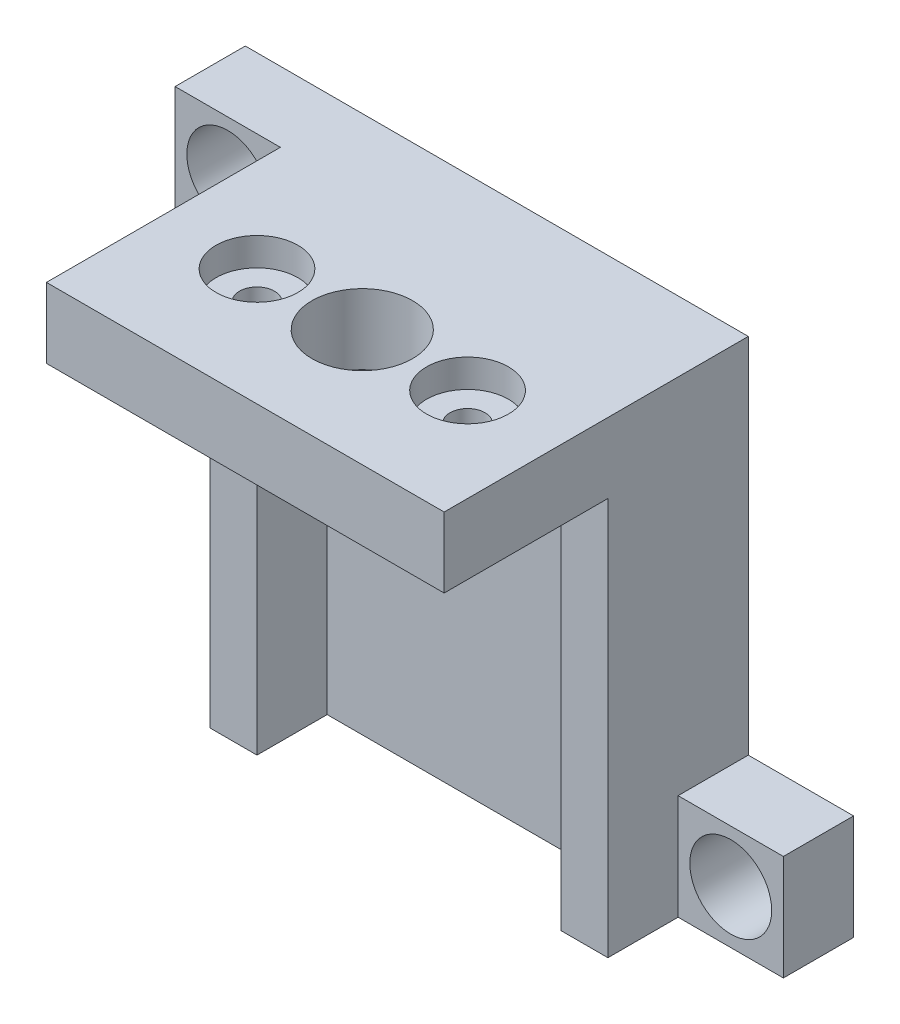
SolidWorks part; units mm, degrees
ref_plane "Front Plane" through (0, 0, 0) normal (0, 0, 1) x (1, 0, 0)
ref_plane "Top Plane" through (0, 0, 0) normal (0, 1, 0) x (1, 0, 0)
ref_plane "Right Plane" through (0, 0, 0) normal (1, 0, 0) x (0, 0, -1)
sketch "Sketch1" plane through (0, 0, 0) normal (0, 0, 1) x (1, 0, 0)
  line L5 (0, 0) -> (17, 0)
  line L6 (0, 0) -> (0, 15.5)
  line L11 (0, 20) -> (17, 20)
  line L12 (17, 4.5) -> (17, 20)
  line L17 (0, 0) -> (17, 20) construction
  line L18 (0, 20) -> (17, 0) construction
  line L19 (0, 20) -> (-4.5, 20)
  line L21 (0, 15.5) -> (-4.5, 15.5)
  line L22 (-4.5, 20) -> (-4.5, 15.5)
  line L23 (0, 20) -> (-4.5, 15.5) construction
  line L24 (0, 15.5) -> (-4.5, 20) construction
  line L25 (17, 0) -> (21.5, 0)
  line L27 (17, 4.5) -> (21.5, 4.5)
  line L28 (21.5, 0) -> (21.5, 4.5)
  line L29 (17, 0) -> (21.5, 4.5) construction
  line L30 (17, 4.5) -> (21.5, 0) construction
  point P4 (8.5, 10)
  point P8 (-2.25, 17.75)
  point P12 (19.25, 2.25)
  dimension "D1" = 20
  dimension "D2" = 17
  dimension "D3" = 4.5
extrude "Boss-Extrude1" add sketch "Sketch1" along normal blind 3
sketch "Sketch2" plane through (0, 0, 3) normal (0, 0, 1) x (1, 0, 0)
  line L5 (0, 15.5) -> (0, 20)
  line L6 (17, 20) -> (-4.5, 20) construction
  line L7 (0, 20) -> (17, 20)
  line L12 (17, 20) -> (17, 0)
  line L13 (0, 0) -> (21.5, 0) construction
  line L18 (17, 0) -> (15, 0)
  line L19 (15, 0) -> (15, 17)
  line L20 (15, 17) -> (2, 17)
  line L21 (2, 17) -> (2, 0)
  line L22 (2, 0) -> (0, 0)
  line L23 (0, 0) -> (0, 15.5)
  dimension "D1" = 3
  dimension "D2" = 2
  dimension "D3" = 2
extrude "Boss-Extrude2" add sketch "Sketch2" along normal blind 3 contours L23 L5 L7 L12 L18 L19 L20 L21 L22
sketch "Sketch3" plane through (0, 20, 0) normal (0, 1, 0) x (1, 0, 0)
  line L5 (0, 0) -> (17, 0)
  line L6 (0, 0) -> (0, -13)
  line L7 (0, -13) -> (17, -13)
  line L8 (17, 0) -> (17, -13)
  line L9 (0, 0) -> (17, -13) construction
  line L10 (0, -13) -> (17, 0) construction
  circle A0 centre (8.5, -8) radius 2.15
  circle A1 centre (13, -8) radius 0.75
  circle A2 centre (4, -8) radius 0.75
  point P4 (8.5, -6.5)
  dimension "D3" = 1.5
  dimension "D4" = 4.3
  dimension "D1" = 13
  dimension "D2" = 17
  dimension "D7" = 4.5
  dimension "D8" = 4.5
extrude "Boss-Extrude3" add sketch "Sketch3" against normal blind 3
sketch "Sketch4" plane through (0, 20, 0) normal (0, -1, 0) x (-1, 0, 0)
  circle A0 centre (-4, -8) radius 1.75
  circle A1 centre (-13, -8) radius 1.75
  dimension "D2" = 3.5
sketch "Sketch6" plane through (0, 17, 0) normal (0, -1, 0) x (-1, 0, 0)
  circle A0 centre (-8.5, -8) radius 2.15
  dimension "D1" = 4.3
extrude "Cut-Extrude2" cut sketch "Sketch6" against normal up to next
sketch "Sketch8" plane through (0, 0, 3) normal (0, 0, 1) x (1, 0, 0)
  line L1 (-4.5, 15.5) -> (0, 15.5) construction
  line L2 (-4.5, 15.5) -> (-4.5, 20) construction
  line L3 (-4.5, 20) -> (0, 20) construction
  line L4 (0, 15.5) -> (0, 20) construction
  line L5 (-4.5, 15.5) -> (0, 20) construction
  line L6 (-4.5, 20) -> (0, 15.5) construction
  line L7 (21.5, 0) -> (17, 0) construction
  line L8 (21.5, 0) -> (21.5, 4.5) construction
  line L9 (21.5, 4.5) -> (17, 4.5) construction
  line L10 (17, 0) -> (17, 4.5) construction
  line L11 (21.5, 0) -> (17, 4.5) construction
  line L12 (21.5, 4.5) -> (17, 0) construction
  circle A0 centre (19.25, 2.25) radius 1.75
  circle A1 centre (-2.25, 17.75) radius 1.75
  point P4 (-2.25, 17.75)
  point P11 (19.25, 2.25)
  dimension "D1" = 3.5
extrude "Cut-Extrude3" cut sketch "Sketch8" against normal up to next
extrude "Cut-Extrude4" cut sketch "Sketch4" along normal blind 1.2
